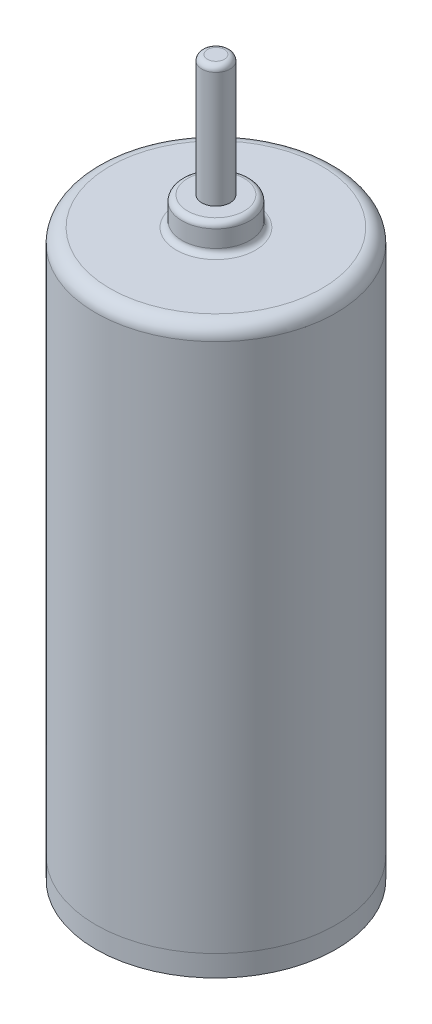
SolidWorks part; units mm, degrees
ref_plane "Front Plane" through (0, 0, 0) normal (0, 0, 1) x (1, 0, 0)
ref_plane "Top Plane" through (0, 0, 0) normal (0, 1, 0) x (1, 0, 0)
ref_plane "Right Plane" through (0, 0, 0) normal (1, 0, 0) x (0, 0, -1)
sketch "Sketch1" plane through (0, 0, 0) normal (0, 1, 0) x (1, 0, 0)
  circle A0 centre (0, 0) radius 4.25
  dimension "D1" = 8.5
extrude "Boss-Extrude1" add sketch "Sketch1" along normal blind 0.75
sketch "Sketch2" plane through (0, 0.75, 0) normal (0, 1, 0) x (1, 0, 0)
  circle A1 centre (0, 0) radius 4.25
  circle A2 centre (0, 0) radius 4.25
  dimension "D1" = 0
extrude "Boss-Extrude2" add sketch "Sketch2" along normal offset from surface (19.25 mm away) 20 separate body up to face at (0, 0, 4.25)
sketch "Sketch3" plane through (0, 20, 0) normal (0, 1, 0) x (1, 0, 0)
  circle A0 centre (0, 0) radius 1.2
  dimension "D1" = 2.4
extrude "Boss-Extrude3" add sketch "Sketch3" along normal blind 1
sketch "Sketch4" plane through (0, 21, 0) normal (0, 1, 0) x (1, 0, 0)
  circle A0 centre (0, 0) radius 0.5
  dimension "D1" = 1
extrude "Boss-Extrude4" add sketch "Sketch4" along normal blind 4.3
fillet "Fillet1" radius 0.5 1 edges at (0, 20, 4.25)
fillet "Fillet2" radius 0.2 3 edges at (0, 25.3, 0.5) (0, 21, 1.2) (0, 20, 1.2)
sketch "Sketch5" plane through (0, 0, 0) normal (0, -1, 0) x (1, 0, 0)
  line L0 (-4.25, 0) -> (4.25, 0) construction
  circle A0 centre (0, 0) radius 4.25 construction
  circle A1 centre (0, 0) radius 2.25
  circle A2 centre (-2.25, 0) radius 0.35
  circle A3 centre (2.25, 0) radius 0.35
  dimension "D1" = 4.5
  dimension "D2" = 0.7
extrude "Boss-Extrude5" add sketch "Sketch5" along normal blind 0.25 contours A2 | A3
